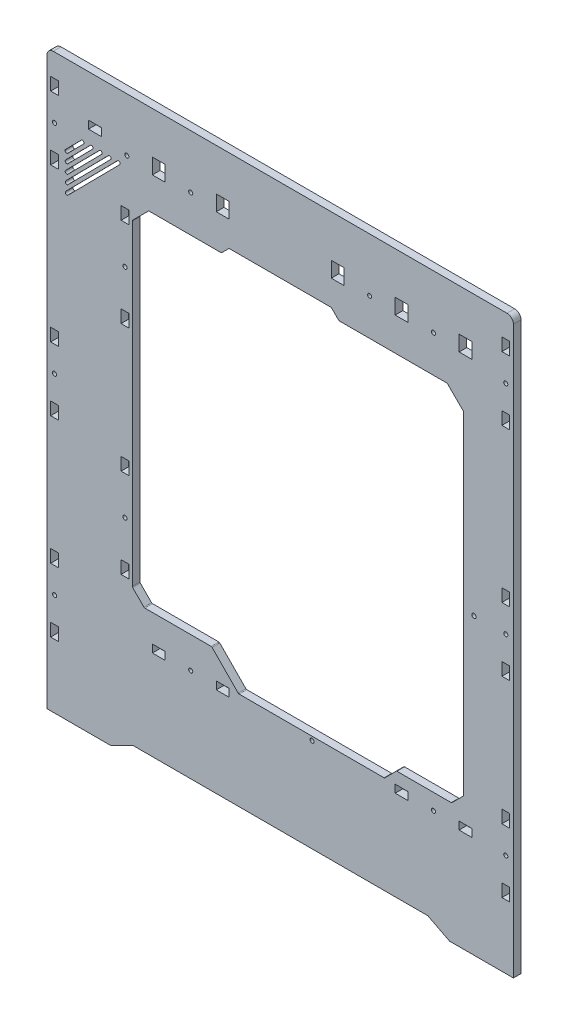
SolidWorks part; units mm, degrees
material "Клен"
ref_plane "Front" through (0, 0, 0) normal (0, 0, 1) x (1, 0, 0)
ref_plane "Top" through (0, 0, 0) normal (0, 1, 0) x (1, 0, 0)
ref_plane "Right" through (0, 0, 0) normal (1, 0, 0) x (0, 0, -1)
sketch "Эскиз1" plane through (0, 0, 0) normal (0, 0, 1) x (1, 0, 0)
  line L0 (830.5087, 490.0072) -> (773.3665, 490.0072)
  line L1 (768.3665, 485.0072) -> (768.3665, 477.0072)
  line L8 (1124.3665, 292.0072) -> (1130.4665, 292.0072)
  line L9 (1124.3665, 302.0072) -> (1124.3665, 292.0072)
  line L10 (1130.4665, 302.0072) -> (1124.3665, 302.0072)
  line L11 (1130.4665, 292.0072) -> (1130.4665, 302.0072)
  line L32 (1133.3665, 42.0072) -> (1133.3665, 477.0072)
  line L39 (909.8665, 490.0072) -> (830.5087, 490.0072)
  line L42 (768.3665, 477.0072) -> (768.3665, 42.0072)
  line L43 (768.3665, 42.0072) -> (818.3665, 42.0072)
  line L44 (818.3665, 42.0072) -> (835.3665, 50.7375)
  line L45 (835.3665, 50.7375) -> (1066.3665, 50.7375)
  line L46 (1066.3665, 50.7375) -> (1083.3665, 42.0072)
  line L47 (1083.3665, 42.0072) -> (1133.3665, 42.0072)
  line L48 (1124.3665, 242.0072) -> (1130.4665, 242.0072)
  line L49 (1124.3665, 252.0072) -> (1124.3665, 242.0072)
  line L50 (1130.4665, 252.0072) -> (1124.3665, 252.0072)
  line L51 (1130.4665, 242.0072) -> (1130.4665, 252.0072)
  line L56 (1124.3665, 142.0072) -> (1130.4665, 142.0072)
  line L57 (1124.3665, 152.0072) -> (1124.3665, 142.0072)
  line L58 (1130.4665, 152.0072) -> (1124.3665, 152.0072)
  line L59 (1130.4665, 142.0072) -> (1130.4665, 152.0072)
  line L64 (1124.3665, 92.0072) -> (1130.4665, 92.0072)
  line L65 (1124.3665, 102.0072) -> (1124.3665, 92.0072)
  line L66 (1130.4665, 102.0072) -> (1124.3665, 102.0072)
  line L67 (1130.4665, 92.0072) -> (1130.4665, 102.0072)
  line L72 (1100.8665, 127.1049) -> (1090.8665, 127.1049)
  line L73 (1100.8665, 121.0049) -> (1100.8665, 127.1049)
  line L74 (1090.8665, 121.0049) -> (1100.8665, 121.0049)
  line L75 (1090.8665, 127.1049) -> (1090.8665, 121.0049)
  line L80 (1050.8665, 127.1049) -> (1040.8665, 127.1049)
  line L81 (1050.8665, 121.0049) -> (1050.8665, 127.1049)
  line L82 (1040.8665, 121.0049) -> (1050.8665, 121.0049)
  line L83 (1040.8665, 127.1049) -> (1040.8665, 121.0049)
  line L96 (910.8665, 121.0049) -> (910.8665, 127.1049)
  line L97 (900.8665, 121.0049) -> (910.8665, 121.0049)
  line L98 (900.8665, 127.1049) -> (900.8665, 121.0049)
  line L99 (910.8665, 127.1049) -> (900.8665, 127.1049)
  line L104 (860.8665, 121.0049) -> (860.8665, 127.1049)
  line L105 (850.8665, 121.0049) -> (860.8665, 121.0049)
  line L106 (850.8665, 127.1049) -> (850.8665, 121.0049)
  line L107 (860.8665, 127.1049) -> (850.8665, 127.1049)
  line L112 (771.2665, 102.0072) -> (771.2665, 92.0072)
  line L113 (777.3665, 102.0072) -> (771.2665, 102.0072)
  line L114 (777.3665, 92.0072) -> (777.3665, 102.0072)
  line L115 (771.2665, 92.0072) -> (777.3665, 92.0072)
  line L120 (771.2665, 152.0072) -> (771.2665, 142.0072)
  line L121 (777.3665, 152.0072) -> (771.2665, 152.0072)
  line L122 (777.3665, 142.0072) -> (777.3665, 152.0072)
  line L123 (771.2665, 142.0072) -> (777.3665, 142.0072)
  line L128 (826.3665, 172.0072) -> (826.3665, 162.0072)
  line L129 (832.4665, 172.0072) -> (826.3665, 172.0072)
  line L130 (832.4665, 162.0072) -> (832.4665, 172.0072)
  line L131 (826.3665, 162.0072) -> (832.4665, 162.0072)
  line L136 (826.3665, 242.0072) -> (826.3665, 232.0072)
  line L137 (832.4665, 242.0072) -> (826.3665, 242.0072)
  line L138 (832.4665, 232.0072) -> (832.4665, 242.0072)
  line L139 (826.3665, 232.0072) -> (832.4665, 232.0072)
  line L144 (771.2665, 252.0072) -> (771.2665, 242.0072)
  line L145 (777.3665, 252.0072) -> (771.2665, 252.0072)
  line L146 (777.3665, 242.0072) -> (777.3665, 252.0072)
  line L147 (771.2665, 242.0072) -> (777.3665, 242.0072)
  line L152 (1124.3665, 412.0072) -> (1130.4665, 412.0072)
  line L153 (1124.3665, 422.0072) -> (1124.3665, 412.0072)
  line L154 (1130.4665, 422.0072) -> (1124.3665, 422.0072)
  line L155 (1130.4665, 412.0072) -> (1130.4665, 422.0072)
  line L160 (1124.3665, 462.0072) -> (1130.4665, 462.0072)
  line L161 (1124.3665, 472.0072) -> (1124.3665, 462.0072)
  line L162 (1130.4665, 472.0072) -> (1124.3665, 472.0072)
  line L163 (1130.4665, 462.0072) -> (1130.4665, 472.0072)
  line L168 (1090.8665, 457.1072) -> (1090.8665, 445.0072)
  line L169 (1100.8665, 457.1072) -> (1090.8665, 457.1072)
  line L170 (1100.8665, 445.0072) -> (1100.8665, 457.1072)
  line L171 (1090.8665, 445.0072) -> (1100.8665, 445.0072)
  line L176 (1040.8665, 457.1072) -> (1040.8665, 445.0072)
  line L177 (1050.8665, 457.1072) -> (1040.8665, 457.1072)
  line L178 (1050.8665, 445.0072) -> (1050.8665, 457.1072)
  line L179 (1040.8665, 445.0072) -> (1050.8665, 445.0072)
  line L184 (990.8665, 457.1072) -> (990.8665, 445.0072)
  line L185 (1000.8665, 457.1072) -> (990.8665, 457.1072)
  line L186 (1000.8665, 445.0072) -> (1000.8665, 457.1072)
  line L187 (990.8665, 445.0072) -> (1000.8665, 445.0072)
  line L192 (900.8665, 445.0072) -> (910.8665, 445.0072)
  line L193 (900.8665, 457.1072) -> (900.8665, 445.0072)
  line L194 (910.8665, 457.1072) -> (900.8665, 457.1072)
  line L195 (910.8665, 445.0072) -> (910.8665, 457.1072)
  line L200 (826.3665, 412.0072) -> (826.3665, 402.0072)
  line L201 (832.4665, 412.0072) -> (826.3665, 412.0072)
  line L202 (832.4665, 402.0072) -> (832.4665, 412.0072)
  line L203 (826.3665, 402.0072) -> (832.4665, 402.0072)
  line L224 (996.2808, 419.7551) -> (991.4523, 424.5835)
  line L225 (1081.1223, 419.1693) -> (997.695, 419.1693)
  line L226 (1094.1201, 406.6723) -> (1081.8269, 418.8789)
  line L227 (1094.4155, 146.42) -> (1094.4155, 405.9627)
  line L228 (1085.3572, 136.8536) -> (1094.1263, 145.7167)
  line L229 (1042.289, 136.5569) -> (1084.6463, 136.5569)
  line L230 (1032.8134, 127.4016) -> (1041.5781, 136.2603)
  line L231 (918.729, 127.1049) -> (1032.1025, 127.1049)
  line L232 (897.5745, 148.2016) -> (918.0158, 127.4039)
  line L233 (844.9385, 148.5006) -> (896.8613, 148.5006)
  line L234 (835.4584, 157.6604) -> (844.2276, 148.7973)
  line L235 (835.1693, 405.9627) -> (835.1693, 158.3637)
  line L236 (847.7579, 418.8789) -> (835.4647, 406.6723)
  line L237 (904.0381, 419.1693) -> (848.4625, 419.1693)
  line L238 (910.2808, 424.5835) -> (905.4523, 419.7551)
  line L239 (990.0381, 425.1693) -> (911.695, 425.1693)
  line L240 (850.8665, 445.0072) -> (860.8665, 445.0072)
  line L241 (850.8665, 457.1072) -> (850.8665, 445.0072)
  line L242 (860.8665, 457.1072) -> (850.8665, 457.1072)
  line L243 (860.8665, 445.0072) -> (860.8665, 457.1072)
  line L244 (784.8721, 398.2711) -> (825.3055, 439.1538)
  line L245 (823.528, 440.9118) -> (783.0946, 400.0291)
  line L248 (784.8331, 405.3421) -> (818.2346, 439.1147)
  line L249 (816.4571, 440.8727) -> (783.0556, 407.1001)
  line L252 (784.794, 412.4131) -> (811.1636, 439.0757)
  line L253 (809.3861, 440.8336) -> (783.0165, 414.171)
  line L256 (784.7549, 419.484) -> (804.0927, 439.0366)
  line L257 (802.3151, 440.7946) -> (782.9774, 421.242)
  line L260 (784.7159, 426.555) -> (797.0217, 438.9975)
  line L261 (795.2442, 440.7555) -> (782.9384, 428.313)
  line L262 (909.8665, 490.0072) -> (1128.3665, 490.0072)
  line L263 (1133.3665, 485.0072) -> (1133.3665, 477.0072)
  line L268 (771.2665, 422.0072) -> (771.2665, 412.0072)
  line L269 (777.3665, 422.0072) -> (771.2665, 422.0072)
  line L270 (777.3665, 412.0072) -> (777.3665, 422.0072)
  line L271 (771.2665, 412.0072) -> (777.3665, 412.0072)
  line L276 (800.8665, 451.0072) -> (810.8665, 451.0072)
  line L277 (800.8665, 457.1072) -> (800.8665, 451.0072)
  line L278 (810.8665, 457.1072) -> (800.8665, 457.1072)
  line L279 (810.8665, 451.0072) -> (810.8665, 457.1072)
  line L284 (771.2665, 472.0072) -> (771.2665, 462.0072)
  line L285 (777.3665, 472.0072) -> (771.2665, 472.0072)
  line L286 (777.3665, 462.0072) -> (777.3665, 472.0072)
  line L287 (771.2665, 462.0072) -> (777.3665, 462.0072)
  line L292 (826.3665, 342.0072) -> (826.3665, 332.0072)
  line L293 (832.4665, 342.0072) -> (826.3665, 342.0072)
  line L294 (832.4665, 332.0072) -> (832.4665, 342.0072)
  line L295 (826.3665, 332.0072) -> (832.4665, 332.0072)
  line L300 (771.2665, 302.0072) -> (771.2665, 292.0072)
  line L301 (777.3665, 302.0072) -> (771.2665, 302.0072)
  line L302 (777.3665, 292.0072) -> (777.3665, 302.0072)
  line L303 (771.2665, 292.0072) -> (777.3665, 292.0072)
  arc A0 (1128.3665, 490.0072) -> (1133.3665, 485.0072) centre (1128.3665, 485.0072) cw
  circle A2 centre (1127.4165, 272.0072) radius 1.6
  circle A4 centre (1102.521, 272.0072) radius 1.7
  circle A6 centre (1127.4165, 122.0072) radius 1.6
  arc A23 (773.3665, 482.0072) -> (768.3665, 477.0072) centre (773.3665, 477.0072) ccw
  circle A24 centre (1070.8665, 124.0549) radius 1.6
  circle A26 centre (975.8665, 124.0549) radius 1.6
  circle A28 centre (880.8665, 124.0549) radius 1.6
  circle A38 centre (774.3165, 122.0072) radius 1.6
  circle A40 centre (829.4165, 202.0072) radius 1.6
  circle A42 centre (774.3165, 272.0072) radius 1.6
  circle A44 centre (1127.4165, 442.0072) radius 1.6
  circle A46 centre (1070.8665, 448.0572) radius 1.6
  circle A48 centre (1020.8665, 448.0572) radius 1.6
  circle A50 centre (880.8665, 448.0572) radius 1.6
  circle A52 centre (830.8665, 448.0572) radius 1.6
  arc A56 (825.3055, 439.1538) -> (823.528, 440.9118) centre (824.4168, 440.0328) ccw
  arc A57 (783.0946, 400.0291) -> (784.8721, 398.2711) centre (783.9834, 399.1501) ccw
  arc A60 (818.2346, 439.1147) -> (816.4571, 440.8727) centre (817.3458, 439.9937) ccw
  arc A61 (783.0556, 407.1001) -> (784.8331, 405.3421) centre (783.9443, 406.2211) ccw
  arc A64 (811.1636, 439.0757) -> (809.3861, 440.8336) centre (810.2749, 439.9546) ccw
  arc A65 (783.0165, 414.171) -> (784.794, 412.4131) centre (783.9053, 413.292) ccw
  arc A82 (991.4523, 424.5835) -> (990.0381, 425.1693) centre (990.0381, 423.1693) ccw
  arc A83 (996.2808, 419.7551) -> (997.695, 419.1693) centre (997.695, 421.1693) ccw
  arc A84 (1081.8269, 418.8789) -> (1081.1223, 419.1693) centre (1081.1223, 418.1693) ccw
  arc A85 (1094.4155, 405.9627) -> (1094.1201, 406.6723) centre (1093.4155, 405.9627) ccw
  arc A86 (1094.1263, 145.7167) -> (1094.4155, 146.42) centre (1093.4155, 146.42) ccw
  arc A87 (1084.6463, 136.5569) -> (1085.3572, 136.8536) centre (1084.6463, 137.5569) ccw
  arc A88 (1042.289, 136.5569) -> (1041.5781, 136.2603) centre (1042.289, 135.5569) ccw
  arc A89 (1032.1025, 127.1049) -> (1032.8134, 127.4016) centre (1032.1025, 128.1049) ccw
  arc A90 (918.0158, 127.4039) -> (918.729, 127.1049) centre (918.729, 128.1049) ccw
  arc A91 (897.5745, 148.2016) -> (896.8613, 148.5006) centre (896.8613, 147.5006) ccw
  arc A92 (844.2276, 148.7973) -> (844.9385, 148.5006) centre (844.9385, 149.5006) ccw
  arc A93 (835.1693, 158.3637) -> (835.4584, 157.6604) centre (836.1693, 158.3637) ccw
  arc A94 (835.4647, 406.6723) -> (835.1693, 405.9627) centre (836.1693, 405.9627) ccw
  arc A95 (848.4625, 419.1693) -> (847.7579, 418.8789) centre (848.4625, 418.1693) ccw
  arc A96 (904.0381, 419.1693) -> (905.4523, 419.7551) centre (904.0381, 421.1693) ccw
  arc A97 (911.695, 425.1693) -> (910.2808, 424.5835) centre (911.695, 423.1693) ccw
  arc A100 (804.0927, 439.0366) -> (802.3151, 440.7946) centre (803.2039, 439.9156) ccw
  arc A101 (782.9774, 421.242) -> (784.7549, 419.484) centre (783.8662, 420.363) ccw
  arc A104 (797.0217, 438.9975) -> (795.2442, 440.7555) centre (796.1329, 439.8765) ccw
  arc A105 (782.9384, 428.313) -> (784.7159, 426.555) centre (783.8271, 427.434) ccw
  circle A106 centre (774.3165, 442.0072) radius 1.6
  circle A108 centre (829.4165, 372.0072) radius 1.6
  arc A109 (773.3665, 490.0072) -> (768.3665, 485.0072) centre (773.3665, 485.0072) ccw
  dimension "D51" = 5
extrude "Бобышка-Вытянуть1" add sketch "Эскиз1" along normal blind 6 contours L0 A109 L1 L42 L43 L44 L45 L46 L47 L32 L263 A0 L262 L39 L11 L8 L9 L10 L51 L48 L49 L50 L59 L56 L57 L58 L67 L64 L65 L66 L75 L72 L73 L74 L83 L80 L81 L82 L99 L96 L97 L98 region at (870.1876, 484.2286, 0)
